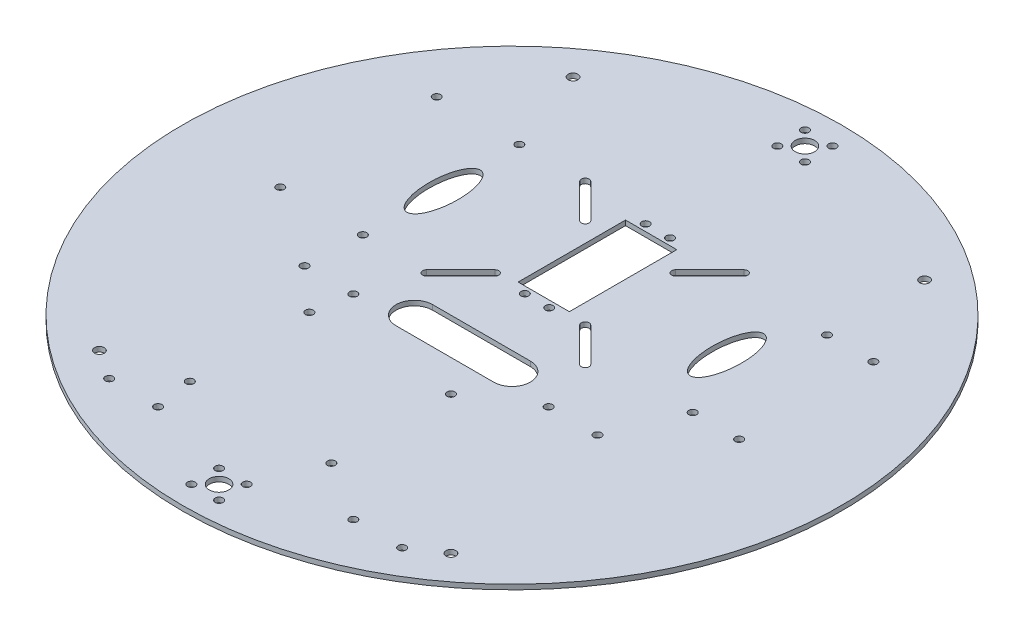
SolidWorks part; units mm, degrees
ref_plane "前视基准面" through (0, 0, 0) normal (0, 0, 1) x (1, 0, 0)
ref_plane "上视基准面" through (0, 0, 0) normal (0, 1, 0) x (1, 0, 0)
ref_plane "右视基准面" through (0, 0, 0) normal (1, 0, 0) x (0, 0, -1)
sketch "草图1" plane through (0, 0, 0) normal (0, 1, 0) x (1, 0, 0)
  line L0 (0, 135) -> (0, -135) construction
  line L1 (-80, 80) -> (80, 80) construction
  line L2 (-80, 80) -> (-80, -80) construction
  line L3 (-80, -80) -> (80, -80) construction
  line L4 (80, 80) -> (80, -80) construction
  line L5 (-80, 80) -> (80, -80) construction
  line L6 (-80, -80) -> (80, 80) construction
  line L7 (-135, 0) -> (135, 0) construction
  line L9 (-30, 60) -> (30, 60) construction
  line L10 (-30, 60) -> (-30, 0) construction
  line L11 (-30, 0) -> (30, 0) construction
  line L12 (30, 60) -> (30, 0) construction
  line L13 (-30, 60) -> (30, 0) construction
  line L14 (-30, 0) -> (30, 60) construction
  circle A0 centre (0, 0) radius 135
  point P17 (0, 0)
  point P19 (0, 30)
  dimension "D1" = 270
  dimension "D2" = 160
  dimension "D3" = 160
  dimension "D5" = 30
  dimension "D6" = 60
  dimension "D7" = 60
extrude "凸台-拉伸1" add sketch "草图1" along normal blind 2
sketch "云台安装孔" plane through (0, 2, 0) normal (0, 1, 0) x (1, 0, 0)
  line L0 (0, 135) -> (0, -135) construction
  line L1 (-135, 0) -> (135, 0) construction
  line L3 (-18.5, 48.5) -> (18.5, 48.5) construction
  line L4 (-18.5, 48.5) -> (-18.5, 11.5) construction
  line L5 (-18.5, 11.5) -> (18.5, 11.5) construction
  line L6 (18.5, 48.5) -> (18.5, 11.5) construction
  line L7 (-18.5, 48.5) -> (18.5, 11.5) construction
  line L8 (-18.5, 11.5) -> (18.5, 48.5) construction
  line L9 (-62.9961, -18.6558) -> (62.9961, -18.6558) construction
  line L10 (-62.9961, -18.6558) -> (-62.9961, -86.2012) construction
  line L11 (-62.9961, -86.2012) -> (62.9961, -86.2012) construction
  line L12 (62.9961, -18.6558) -> (62.9961, -86.2012) construction
  line L13 (-62.9961, -18.6558) -> (62.9961, -86.2012) construction
  line L14 (-62.9961, -86.2012) -> (62.9961, -18.6558) construction
  line L15 (-10.5, 57) -> (10.5, 57)
  line L16 (-10.5, 57) -> (-10.5, 13)
  line L17 (-10.5, 13) -> (10.5, 13)
  line L18 (10.5, 57) -> (10.5, 13)
  line L19 (-10.5, 57) -> (10.5, 13) construction
  line L20 (-10.5, 13) -> (10.5, 57) construction
  line L21 (-5, 59.75) -> (5, 59.75) construction
  line L22 (-5, 59.75) -> (-5, 10.25) construction
  line L23 (-5, 10.25) -> (5, 10.25) construction
  line L24 (5, 59.75) -> (5, 10.25) construction
  line L25 (-5, 59.75) -> (5, 10.25) construction
  line L26 (-5, 10.25) -> (5, 59.75) construction
  line L27 (-38.5, 68.5) -> (38.5, 68.5) construction
  line L28 (-38.5, 68.5) -> (-38.5, -8.5) construction
  line L29 (-38.5, -8.5) -> (38.5, -8.5) construction
  line L30 (38.5, 68.5) -> (38.5, -8.5) construction
  line L31 (-38.5, 68.5) -> (38.5, -8.5) construction
  line L32 (-38.5, -8.5) -> (38.5, 68.5) construction
  circle A0 centre (0, 0) radius 135 construction
  circle A1 centre (-5, 59.75) radius 1.6
  circle A2 centre (5, 59.75) radius 1.6
  circle A3 centre (-5, 10.25) radius 1.6
  circle A4 centre (5, 10.25) radius 1.6
  circle A5 centre (18.5, 48.5) radius 1.6
  circle A6 centre (18.5, 11.5) radius 1.6
  circle A7 centre (-18.5, 11.5) radius 1.6
  circle A8 centre (-18.5, 48.5) radius 1.6
  point P3 (0, 30)
  point P8 (0, 30)
  point P13 (0, -52.4285)
  point P18 (0, 35)
  point P23 (0, 35)
  point P50 (0, 30)
  dimension "D3" = 21
  dimension "D8" = 3.2
  dimension "D9" = 3.2
  dimension "D10" = 3.2
  dimension "D11" = 3.2
  dimension "D12" = 3.2
  dimension "D13" = 3.2
  dimension "D1" = 37
  dimension "D2" = 37
  dimension "D4" = 44
  dimension "D5" = 5
  dimension "D6" = 10
  dimension "D7" = 49.5
  dimension "D14" = 30
  dimension "D15" = 77
  dimension "D16" = 77
extrude "切除-拉伸1" cut sketch "云台安装孔" against normal blind 10
sketch "扩展板安装孔" plane through (0, 2, 0) normal (0, 1, 0) x (1, 0, 0)
  line L0 (0, 135) -> (0, -135) construction
  line L1 (15.5, -40.5) -> (15.5, -89.5) construction
  line L2 (-60, -25) -> (60, -25) construction
  line L3 (-60, -25) -> (-60, -105) construction
  line L4 (-60, -105) -> (60, -105) construction
  line L5 (60, -25) -> (60, -105) construction
  line L6 (-60, -25) -> (60, -105) construction
  line L7 (-60, -105) -> (60, -25) construction
  line L8 (-40, -25) -> (40, -25) construction
  line L9 (-40, -25) -> (-40, -105) construction
  line L10 (-40, -105) -> (40, -105) construction
  line L11 (40, -25) -> (40, -105) construction
  line L12 (-40, -25) -> (40, -105) construction
  line L13 (-40, -105) -> (40, -25) construction
  line L14 (-42.5, -40.5) -> (42.5, -40.5) construction
  line L15 (-42.5, -40.5) -> (-42.5, -89.5) construction
  line L16 (-42.5, -89.5) -> (42.5, -89.5) construction
  line L17 (42.5, -40.5) -> (42.5, -89.5) construction
  line L18 (-42.5, -40.5) -> (42.5, -89.5) construction
  line L19 (-42.5, -89.5) -> (42.5, -40.5) construction
  circle A0 centre (0, 0) radius 135 construction
  circle A1 centre (-60, -25) radius 1.6
  circle A2 centre (-40, -25) radius 1.6
  circle A3 centre (40, -25) radius 1.6
  circle A4 centre (60, -25) radius 1.6
  circle A5 centre (60, -105) radius 1.6
  circle A6 centre (40, -105) radius 1.6
  circle A7 centre (-40, -105) radius 1.6
  circle A8 centre (-60, -105) radius 1.6
  circle A9 centre (-42.5, -89.5) radius 1.6
  circle A12 centre (-42.5, -40.5) radius 1.6
  circle A13 centre (15.5, -40.5) radius 1.6
  circle A14 centre (15.5, -89.5) radius 1.6
  point P5 (0, -65)
  point P10 (0, -65)
  point P15 (0, -65)
  dimension "D7" = 65
  dimension "D1" = 120
  dimension "D2" = 80
  dimension "D3" = 80
  dimension "D4" = 85
  dimension "D5" = 49
  dimension "D6" = 58
extrude "切除-拉伸2" cut sketch "扩展板安装孔" against normal blind 10
sketch "草图4" plane through (0, 2, 0) normal (0, 1, 0) x (1, 0, 0)
  line L0 (0, 135) -> (0, -135) construction
  line L1 (-135, 0) -> (135, 0) construction
  line L2 (-20, -12.5) -> (20, -12.5)
  line L3 (-20, -12.5) -> (-20, -27.5) construction
  line L4 (-20, -27.5) -> (20, -27.5)
  line L5 (20, -12.5) -> (20, -27.5) construction
  line L6 (-20, -12.5) -> (20, -27.5) construction
  line L7 (-20, -27.5) -> (20, -12.5) construction
  line L8 (-72, 97) -> (72, 97) construction
  line L9 (-72, 97) -> (-72, -97) construction
  line L10 (-72, -97) -> (72, -97) construction
  line L11 (72, 97) -> (72, -97) construction
  line L12 (-72, 97) -> (72, -97) construction
  line L13 (-72, -97) -> (72, 97) construction
  circle A0 centre (0, 0) radius 135 construction
  arc A1 (-20, -12.5) -> (-20, -27.5) centre (-20, -20) ccw
  arc A2 (20, -12.5) -> (20, -27.5) centre (20, -20) cw
  circle A3 centre (-72, 97) radius 2
  circle A4 centre (72, 97) radius 2
  circle A5 centre (72, -97) radius 2
  circle A6 centre (-72, -97) radius 2
  circle A7 centre (0, -120) radius 4
  circle A8 centre (0, 120) radius 8 construction
  circle A9 centre (-5.6569, -125.6569) radius 1.6
  circle A10 centre (-5.6569, -114.3431) radius 1.6
  circle A11 centre (5.6569, -114.3431) radius 1.6
  circle A12 centre (5.6569, -125.6569) radius 1.6
  circle A13 centre (5.6569, 125.6569) radius 1.6
  circle A14 centre (5.6569, 114.3431) radius 1.6
  circle A15 centre (-5.6569, 114.3431) radius 1.6
  circle A16 centre (-5.6569, 125.6569) radius 1.6
  circle A17 centre (0, -120) radius 8 construction
  circle A18 centre (0, 120) radius 4
  point P5 (0, -20)
  point P12 (0, 0)
  point P41 (0, -120)
  point P50 (0, 120)
  dimension "D5" = 120
  dimension "D6" = 4
  dimension "D7" = 4
  dimension "D8" = 4
  dimension "D9" = 4
  dimension "D12" = 4
  dimension "D10" = 16
  dimension "D11" = 4
  dimension "D1" = 15
  dimension "D2" = 40
  dimension "D3" = 144
  dimension "D4" = 194
  dimension "D13" = 20
extrude "切除-拉伸3" cut sketch "草图4" against normal blind 10
sketch "草图5" plane through (0, 2, 0) normal (0, 1, 0) x (1, 0, 0)
  line L0 (-31.3686, 63.6314) -> (-17.3686, 49.6314)
  line L1 (-10.5, 57) -> (-10.5, 13) construction
  line L2 (-33.6314, 61.3686) -> (-19.6314, 47.3686)
  line L3 (-32.5, 62.5) -> (32.5, 62.5) construction
  line L4 (-32.5, 62.5) -> (-32.5, -2.5) construction
  line L5 (-32.5, -2.5) -> (32.5, -2.5) construction
  line L6 (32.5, 62.5) -> (32.5, -2.5) construction
  line L7 (-32.5, 62.5) -> (32.5, -2.5) construction
  line L8 (-32.5, -2.5) -> (32.5, 62.5) construction
  line L9 (33.6314, 61.3686) -> (19.6314, 47.3686)
  line L10 (31.3686, 63.6314) -> (17.3686, 49.6314)
  line L11 (31.3686, -3.6314) -> (17.3686, 10.3686)
  line L12 (33.6314, -1.3686) -> (19.6314, 12.6314)
  line L13 (-33.6314, -1.3686) -> (-19.6314, 12.6314)
  line L14 (-31.3686, -3.6314) -> (-17.3686, 10.3686)
  arc A0 (33.6314, 61.3686) -> (31.3686, 63.6314) centre (32.5, 62.5) ccw
  arc A1 (-19.6314, 47.3686) -> (-17.3686, 49.6314) centre (-18.5, 48.5) ccw
  arc A2 (-31.3686, 63.6314) -> (-33.6314, 61.3686) centre (-32.5, 62.5) ccw
  arc A3 (17.3686, 49.6314) -> (19.6314, 47.3686) centre (18.5, 48.5) ccw
  arc A4 (31.3686, -3.6314) -> (33.6314, -1.3686) centre (32.5, -2.5) ccw
  arc A5 (19.6314, 12.6314) -> (17.3686, 10.3686) centre (18.5, 11.5) ccw
  arc A6 (-33.6314, -1.3686) -> (-31.3686, -3.6314) centre (-32.5, -2.5) ccw
  arc A7 (-17.3686, 10.3686) -> (-19.6314, 12.6314) centre (-18.5, 11.5) ccw
  point P5 (0, 30)
  point P35 (0, 30)
  dimension "D4" = 3.2
  dimension "D1" = 30
  dimension "D2" = 10.5
  dimension "D3" = 65
  dimension "D5" = 1.6
  dimension "D6" = 4
extrude "切除-拉伸4" cut sketch "草图5" against normal blind 10
sketch "草图6" plane through (0, 2, 0) normal (0, 1, 0) x (1, 0, 0)
  line L0 (33.6314, -3.6314) -> (33.6314, 63.6314) construction
  line L1 (33.6314, 30) -> (118.3005, 30) construction
  line L2 (0, 120) -> (0, -27.5) construction
  line L3 (-20, -27.5) -> (20, -27.5) construction
  line L4 (-33.6314, -3.6314) -> (-33.6314, 63.6314) construction
  line L5 (71.5372, 2.5) -> (90.5372, 2.5) construction
  line L6 (71.5372, 2.5) -> (71.5372, 57.5) construction
  line L7 (71.5372, 57.5) -> (90.5372, 57.5) construction
  line L8 (90.5372, 2.5) -> (90.5372, 57.5) construction
  line L9 (71.5372, 2.5) -> (90.5372, 57.5) construction
  line L10 (71.5372, 57.5) -> (90.5372, 2.5) construction
  line L11 (-33.6314, 30) -> (-118.3005, 30) construction
  line L14 (-92.886, -2.05) -> (-59.046, -2.05) construction
  line L15 (-92.886, -2.05) -> (-92.886, 62.05) construction
  line L16 (-92.886, 62.05) -> (-59.046, 62.05) construction
  line L17 (-59.046, -2.05) -> (-59.046, 62.05) construction
  line L18 (-92.886, -2.05) -> (-59.046, 62.05) construction
  line L19 (-92.886, 62.05) -> (-59.046, -2.05) construction
  arc A0 (31.3686, -3.6314) -> (33.6314, -1.3686) centre (32.5, -2.5) ccw construction
  arc A1 (33.6314, 61.3686) -> (31.3686, 63.6314) centre (32.5, 62.5) ccw construction
  circle A2 centre (71.5372, 2.5) radius 1.6
  circle A3 centre (90.5372, 2.5) radius 1.6
  circle A4 centre (90.5372, 57.5) radius 1.6
  circle A5 centre (71.5372, 57.5) radius 1.6
  circle A6 centre (-92.886, -2.05) radius 1.6
  circle A7 centre (-59.046, -2.05) radius 1.6
  circle A8 centre (-92.886, 62.05) radius 1.6
  circle A9 centre (-59.046, 62.05) radius 1.6
  ellipse E0 centre (-58.0311, 30) end of major axis (-58.0311, 15) minor radius 6
  ellipse E1 centre (58.0311, 30) end of major axis (58.0311, 45) minor radius 6
  point P15 (81.0372, 30)
  point P49 (-75.966, 30)
  dimension "D3" = 6
  dimension "D1" = 19
  dimension "D2" = 55
  dimension "D4" = 15
  dimension "D5" = 33.84
  dimension "D6" = 64.1
extrude "切除-拉伸7" cut sketch "草图6" against normal blind 10 contours A7 | A2 | A3 | A4 | A5 | E0 | E1 | A6 | A8 | A9
